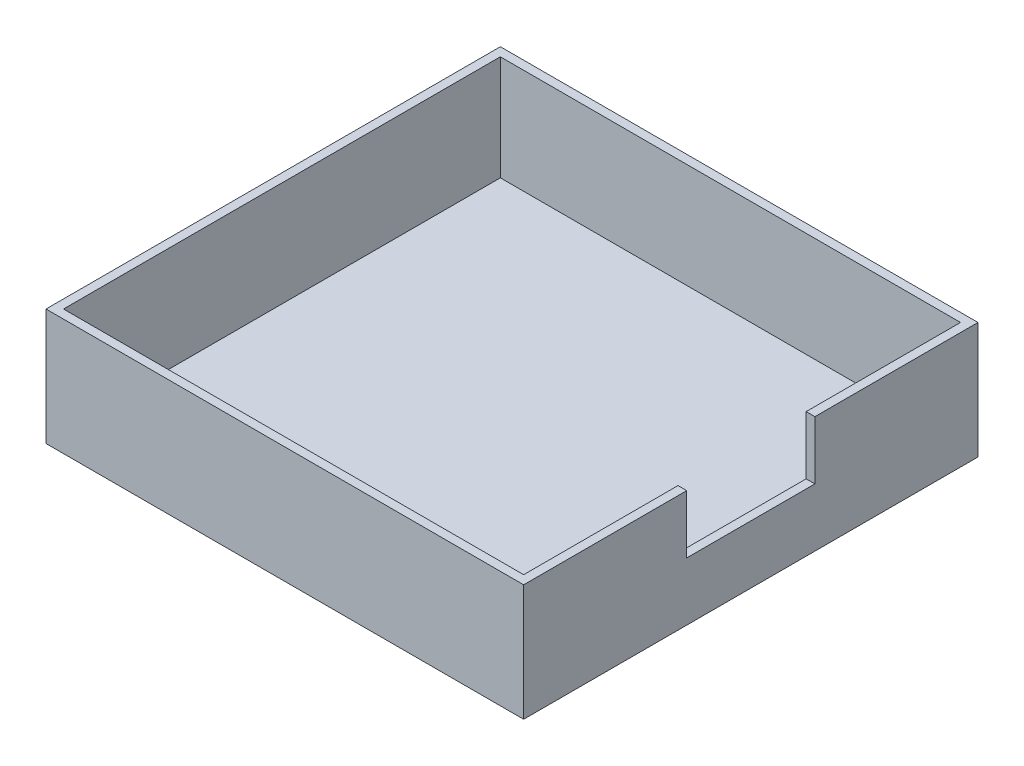
SolidWorks part; units mm, degrees
ref_plane "Alzado" through (0, 0, 0) normal (0, 0, 1) x (1, 0, 0)
ref_plane "Planta" through (0, 0, 0) normal (0, 1, 0) x (1, 0, 0)
ref_plane "Vista lateral" through (0, 0, 0) normal (1, 0, 0) x (0, 0, -1)
sketch "Croquis1" plane through (0, 0, 0) normal (0, 1, 0) x (1, 0, 0)
  line L1 (-39.5, 37.5) -> (39.5, 37.5)
  line L2 (-39.5, 37.5) -> (-39.5, -37.5)
  line L3 (-39.5, -37.5) -> (39.5, -37.5)
  line L4 (39.5, 37.5) -> (39.5, -37.5)
  line L5 (-39.5, 37.5) -> (39.5, -37.5) construction
  line L6 (-39.5, -37.5) -> (39.5, 37.5) construction
  line L7 (-41, 39) -> (41, 39)
  line L8 (-41, 39) -> (-41, -39)
  line L9 (-41, -39) -> (41, -39)
  line L10 (41, 39) -> (41, -39)
  line L11 (-41, 39) -> (41, -39) construction
  line L12 (-41, -39) -> (41, 39) construction
  line L13 (39.5, 11) -> (41, 11)
  line L14 (39.5, 11) -> (39.5, -11)
  line L15 (39.5, -11) -> (41, -11)
  line L16 (41, 11) -> (41, -11)
  point P0 (0, 0)
  point P6 (0, 0)
  dimension "D1" = 75
  dimension "D2" = 79
  dimension "D3" = 78
  dimension "D4" = 82
  dimension "D5" = 22
  dimension "D6" = 28
extrude "Saliente-Extruir1" add sketch "Croquis1" along normal blind 2 contours L2 L1 L4 L3
extrude "Saliente-Extruir3" add sketch "Croquis1<4>" along normal blind 20 contours L15 L4 L3 L2 L1 L13 L10 L7 L8 L9 region at (-40.6317, 0, 0)
sketch "Croquis1<4>" plane through (0, 0, 0) normal (0, 1, 0) x (1, 0, 0) same geometry as "Croquis1"
extrude "Saliente-Extruir4" add sketch "Croquis1<5>" along normal blind 10 contours L4 L15 L10 L13 region at (40.25, 0, 0)
sketch "Croquis1<5>" plane through (0, 0, 0) normal (0, 1, 0) x (1, 0, 0) same geometry as "Croquis1"
